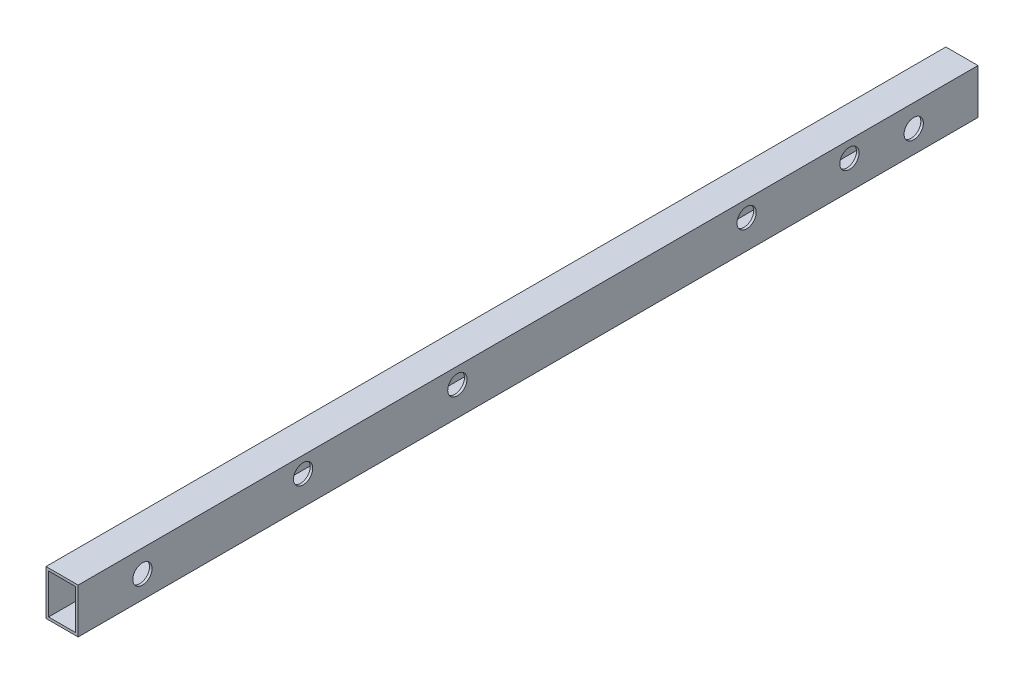
SolidWorks part; units mm, degrees
ref_plane "Front Plane" through (0, 0, 0) normal (0, 0, 1) x (1, 0, 0)
ref_plane "Top Plane" through (0, 0, 0) normal (0, 1, 0) x (1, 0, 0)
ref_plane "Right Plane" through (0, 0, 0) normal (1, 0, 0) x (0, 0, -1)
sketch "Sketch1" plane through (0, 0, 0) normal (0, 0, 1) x (1, 0, 0)
  line L1 (0, 0) -> (50, 0)
  line L2 (0, 0) -> (0, -70)
  line L3 (0, -70) -> (50, -70)
  line L4 (50, 0) -> (50, -70)
  line L5 (4, -4) -> (46, -4)
  line L6 (4, -4) -> (4, -66)
  line L7 (4, -66) -> (46, -66)
  line L8 (46, -4) -> (46, -66)
  dimension "D1" = 70
  dimension "D2" = 50
  dimension "D3" = 4
  dimension "D4" = 4
  dimension "D5" = 4
  dimension "D6" = 4
extrude "Boss-Extrude2" add sketch "Sketch1" along normal blind 1400
sketch "Sketch2" plane through (50, 0, 0) normal (1, 0, 0) x (0, 0, -1)
  line L0 (-1400, -70) -> (-1400, 0) construction
  line L1 (-1400, 0) -> (0, 0) construction
  circle A0 centre (-1050, -25) radius 15
  circle A1 centre (-200, -25) radius 15
  circle A2 centre (-810, -25) radius 15
  circle A3 centre (-360, -25) radius 15
  dimension "D1" = 30
  dimension "D2" = 30
  dimension "D3" = 30
  dimension "D4" = 30
  dimension "D5" = 350
  dimension "D6" = 240
  dimension "D7" = 450
  dimension "D8" = 160
  dimension "D9" = 25
extrude "Cut-Extrude1" cut sketch "Sketch2" against normal through all
sketch "Sketch3" plane through (50, 0, 0) normal (1, 0, 0) x (0, 0, -1)
  line L0 (-1400, -70) -> (-1400, 0) construction
  line L2 (-1400, 0) -> (0, 0) construction
  line L3 (0, -70) -> (0, 0) construction
  circle A0 centre (-1300, -35) radius 15
  circle A1 centre (-100, -35) radius 15
  point P7 (0, 0)
  dimension "D1" = 30
  dimension "D4" = 30
  dimension "D2" = 100
  dimension "D3" = 35
  dimension "D5" = 100
extrude "Cut-Extrude2" cut sketch "Sketch3" against normal through all
equation "\"D4@Sketch1\"=\"D3@Sketch1\""
equation "\"D5@Sketch1\"=\"D3@Sketch1\""
equation "\"D2@Sketch2\"=\"D1@Sketch2\""
